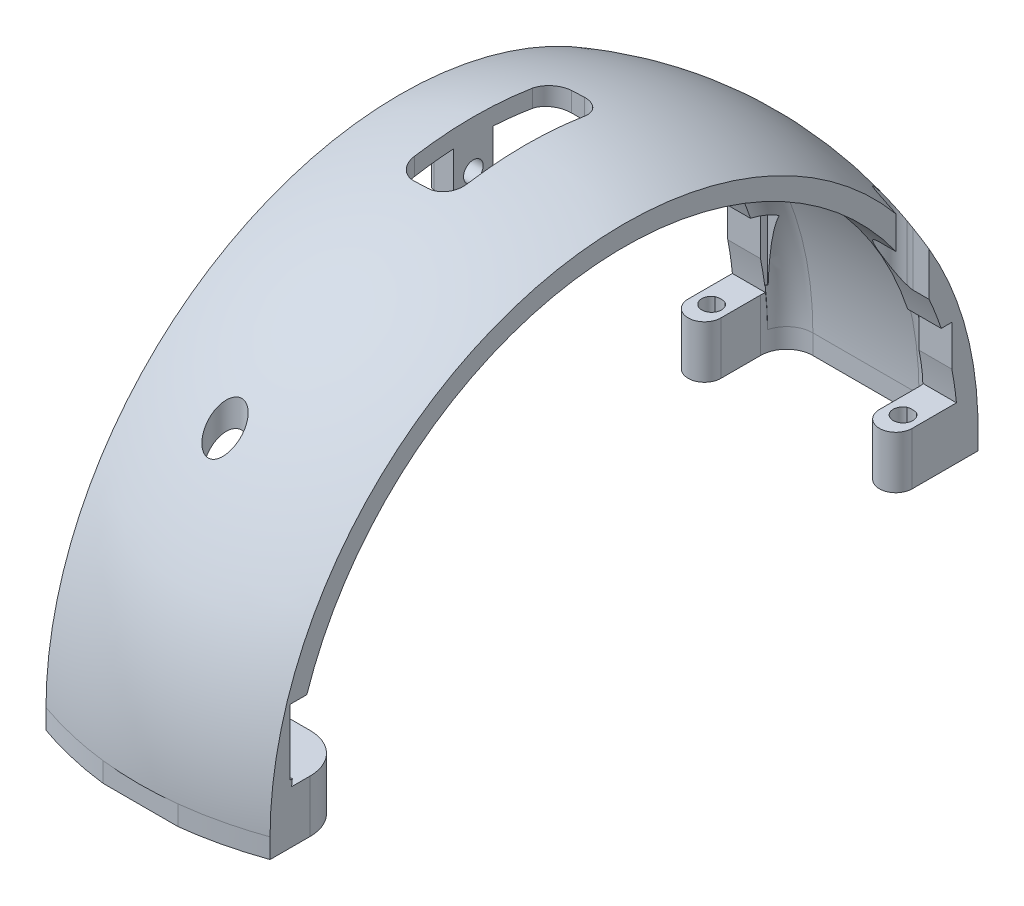
SolidWorks part; units mm, degrees
ref_plane "Front Plane" through (0, 0, 0) normal (0, 0, 1) x (1, 0, 0)
ref_plane "Top Plane" through (0, 0, 0) normal (0, 1, 0) x (1, 0, 0)
ref_plane "Right Plane" through (0, 0, 0) normal (1, 0, 0) x (0, 0, -1)
sketch "Sketch1" plane through (0, 0, 0) normal (0, 1, 0) x (1, 0, 0)
  line L0 (0, 55) -> (0, -55) construction
  line L1 (-55, 0) -> (55, 0)
  line L2 (-55, 20.7263) -> (-55, -21.0382) construction
  line L3 (-6.2, 54.0459) -> (10.01, 54.0459)
  line L4 (-15.2, 44) -> (-10.2, 44)
  line L5 (-15.2, 44) -> (-15.2, 54.0459)
  line L7 (-10.2, 44) -> (-10.2, 50.0459)
  line L12 (1.905, 54.0459) -> (1.905, 57.0459) construction
  line L13 (19.01, 44) -> (14.01, 44)
  line L14 (19.01, 44) -> (19.01, 54.0459)
  line L16 (14.01, 44) -> (14.01, 50.0459)
  line L17 (-10.2, 50.0459) -> (-15.2, 50.0459)
  line L22 (2.5, -41.91) -> (-2.5, -41.91)
  line L23 (2.5, -41.91) -> (2.5, -56.71)
  line L24 (2.5, -56.71) -> (-2.5, -56.71)
  line L25 (-2.5, -41.91) -> (-2.5, -56.71)
  line L26 (14.01, 50.0459) -> (19.01, 50.0459)
  line L27 (-2.5, -48.71) -> (2.5, -48.71)
  line L28 (-2.5, -15.41) -> (2.5, -15.41) construction
  line L29 (-2.5, -52.2226) -> (2.5, -52.2226)
  line L30 (16.51, 41.5) -> (19.01, 41.5)
  line L31 (16.51, 41.5) -> (16.51, 44)
  line L32 (16.51, 44) -> (19.01, 44)
  line L33 (19.01, 41.5) -> (19.01, 44)
  line L34 (-12.7, 41.5) -> (-15.2, 41.5)
  line L35 (-12.7, 41.5) -> (-12.7, 44)
  line L36 (-12.7, 44) -> (-15.2, 44)
  line L37 (-15.2, 41.5) -> (-15.2, 44)
  line L51 (-5, 0) -> (0, 0)
  line L54 (0, -4) -> (0, 4)
  line L55 (-16, 0) -> (-21, 0)
  line L73 (7, -3) -> (4, -3)
  line L74 (-1, 12) -> (1, 12)
  line L75 (-4, 9) -> (-4, -9)
  line L76 (-1, -12) -> (1, -12)
  line L77 (4, 9) -> (4, -9)
  line L78 (-4, 12) -> (4, -12) construction
  line L79 (-4, -12) -> (4, 12) construction
  line L80 (-7, 3) -> (-4, 3)
  line L81 (-8, 2) -> (-8, -2)
  line L82 (-7, -3) -> (-4, -3)
  line L83 (-4, 3) -> (-4, -3)
  line L84 (-8, 3) -> (-4, -3) construction
  line L85 (-8, -3) -> (-4, 3) construction
  line L86 (4, 3) -> (4, -3)
  line L87 (7, 3) -> (4, 3)
  line L88 (8, 2) -> (8, -2)
  line L90 (-35, 51) -> (35, 51)
  line L91 (-35, 51) -> (-35, -51)
  line L92 (-35, -51) -> (35, -51)
  line L93 (35, 51) -> (35, -51)
  line L94 (-35, 51) -> (35, -51) construction
  line L95 (-35, -51) -> (35, 51) construction
  circle A0 centre (0, 0) radius 55 construction
  circle A1 centre (0, -41.91) radius 1.5 construction
  circle A2 centre (16.5327, 45.0784) radius 1.5 construction
  arc A3 (1, -12) -> (4, -9) centre (1, -9) ccw
  circle A4 centre (0, -41.91) radius 1.5
  circle A8 centre (-12.7, 44) radius 2.5
  circle A9 centre (16.51, 44) radius 2.5
  circle A10 centre (0, -41.91) radius 2.5
  arc A11 (14.01, 50.0459) -> (10.01, 54.0459) centre (10.01, 50.0459) ccw
  arc A12 (-6.2, 54.0459) -> (-10.2, 50.0459) centre (-6.2, 50.0459) ccw
  circle A13 centre (0, 0) radius 50 construction
  circle A14 centre (-12.7049, 45.0912) radius 1.5 construction
  circle A15 centre (16.5327, 45.0784) radius 1.5
  circle A16 centre (-12.7049, 45.0912) radius 1.5
  arc A17 (-4, -9) -> (-1, -12) centre (-1, -9) ccw
  arc A18 (1, 12) -> (4, 9) centre (1, 9) cw
  arc A19 (-4, 9) -> (-1, 12) centre (-1, 9) cw
  arc A20 (8, -2) -> (7, -3) centre (7, -2) cw
  arc A21 (8, 2) -> (7, 3) centre (7, 2) ccw
  arc A22 (-8, -2) -> (-7, -3) centre (-7, -2) ccw
  arc A23 (-8, 2) -> (-7, 3) centre (-7, 2) cw
  spline S0 degree 2 poles (-15.2, 54.0459) (1.905, 60.0459) (19.01, 54.0459) knots 0 0 0 1 1 1
  point P59 (-6, 0)
  point P87 (8, -3)
  point P90 (8, 3)
  dimension "D1" = 110
  dimension "D2" = 5
  dimension "D3" = 5
  dimension "D4" = 100
  dimension "D5" = 8
  dimension "D6" = 3
  dimension "D7" = 5
  dimension "D10" = 4
  dimension "D12" = 24
  dimension "D11" = 8
  dimension "D13" = 4
  dimension "D16" = 3
  dimension "D17" = 1
  dimension "D8" = 5
  dimension "D9" = 14.8
  dimension "D14" = 6
  dimension "D15" = 4
  dimension "D18" = 102
  dimension "D19" = 70
extrude "Boss-Extrude1" add sketch "Sketch1" along normal blind 2 contours A16 A8 L7 L17 L5 | S0 L5 L17 A12 L3 A11 L26 L14 | A16 L35 A8 L4 | A16 L4 A8 L35 | A16 A8 L4 | A16 L4 A8 | A8 A16 | A15 A9 L14 L26 L16 | A15 L13 A9 L31 | A15 L31 A9 L13 | A15 L13 A9 | A15 A9 L13 | A9 A15 | A12 L90 L5 L17 | A11 L26 L14 L90 region at (-12.6808, 0, -50.5248) region at (1.905, 0, -54.3281) region at (-12.6999, 0, -47.9735) region at (-14.5064, 0, -44.8299) region at (-13.8029, 0, -42.8825) region at (16.4908, 0, -50.5248) region at (-11.5974, 0, -42.8833) region at (-12.7113, 0, -46.5121) region at (-10.9002, 0, -44.8348) region at (16.5098, 0, -47.9721) region at (14.7243, 0, -44.8518) region at (15.4064, 0, -42.8824) region at (17.6152, 0, -42.8786) region at (18.3266, 0, -44.8292) region at (16.5628, 0, -46.5096)
revolve "Revolve6" add sketch "Sketch1<7>" angle 180 about L1 region at (1.905, 0, -54.3281)
sketch "Sketch1<7>" plane through (0, 0, 0) normal (0, 1, 0) x (1, 0, 0) same geometry as "Sketch1"
extrude "Cut-Extrude1" cut sketch "Sketch1<9>" along normal blind 50 from surface contours A16 L35 A8 L4 | A16 L4 A8 L35 | A16 A8 L4 | A16 L4 A8 | L4 A16 A8 L36 | L36 A16 L35 | L35 A16 L4 | A8 A16 | A9 A15 | L32 A15 A9 L13 | A15 A9 L13 | A15 L13 A9 | A15 L31 A9 L13 | A15 L13 A9 L31 | L13 A15 L31 | L31 A15 L32 | L22 A10 A4 | L22 A4 | L22 A4 | L22 A10 A4 | A9 L30 L33 | A8 L37 L34 region at (-14.5064, 0, -44.8299) region at (-14.6416, 0, -42.0584) region at (-13.8029, 0, -42.8825) region at (0, 0, 39.4659) region at (-2, 0, 41.9659) region at (-12.7048, 0, -45.1835) region at (-13.0962, 0, -43.8342) region at (-11.5974, 0, -42.8833) region at (-12.7113, 0, -46.5121) region at (-10.9002, 0, -44.8348) region at (0, 0, 41.2734) region at (0, 0, 42.5466) region at (-12.3081, 0, -43.8347) region at (14.7243, 0, -44.8518) region at (15.4064, 0, -42.8824) region at (17.6152, 0, -42.8786) region at (18.4516, 0, -42.0584) region at (18.3266, 0, -44.8292) region at (16.5323, 0, -45.1793) region at (16.1205, 0, -43.8304) region at (16.5628, 0, -46.5096) region at (16.9196, 0, -43.8279) starting at face at (-12.7047, 2, -45.0456)
sketch "Sketch1<9>" plane through (0, 0, 0) normal (0, 1, 0) x (1, 0, 0) same geometry as "Sketch1"
extrude "Boss-Extrude2" add sketch "Sketch1<11>" along normal blind 2 and the other way blind 3 separate body contours A10 L25 L27 L23 | L22 A10 A4 | L22 A10 A4 | L25 L29 L23 L27 | L25 L92 L23 L27 | L29 L25 L24 L23 region at (0, 0, 51.6113) region at (0, 0, 49.855) region at (0, 0, 46.2596) region at (0, 0, 54.4663) region at (0, 0, 39.4659) region at (-2, 0, 41.9659)
sketch "Sketch1<11>" plane through (0, 0, 0) normal (0, 1, 0) x (1, 0, 0) same geometry as "Sketch1"
extrude "Boss-Extrude3" add sketch "Sketch1<12>" against normal blind 3 contours A10 L25 L27 L23 | L22 A10 A4 | L22 A10 A4 | S0 L5 L17 A12 L3 A11 L26 L14 | A16 A8 L7 L17 L5 | A15 A9 L14 L26 L16 | A15 L31 A9 L13 | A15 L13 A9 L31 | A16 L35 A8 L4 | A16 L4 A8 L35 | A15 L13 A9 | A15 A9 L13 | A16 L4 A8 | A16 A8 L4 | A9 A15 | A11 L26 L14 L90 | A12 L90 L5 L17 | L92 L25 L29 L23 | L25 L92 L23 L27 region at (-12.6808, 0, -50.5248) region at (1.905, 0, -54.3281) region at (0, 0, 51.6113) region at (0, 0, 49.855) region at (-12.6999, 0, -47.9735) region at (0, 0, 46.2596) region at (-14.5064, 0, -44.8299) region at (-13.8029, 0, -42.8825) region at (16.4908, 0, -50.5248) region at (0, 0, 39.4659) region at (-2, 0, 41.9659) region at (-11.5974, 0, -42.8833) region at (-10.9002, 0, -44.8348) region at (16.5098, 0, -47.9721) region at (14.7243, 0, -44.8518) region at (15.4064, 0, -42.8824) region at (17.6152, 0, -42.8786) region at (18.3266, 0, -44.8292) region at (16.5628, 0, -46.5096)
sketch "Sketch1<12>" plane through (0, 0, 0) normal (0, 1, 0) x (1, 0, 0) same geometry as "Sketch1"
extrude "Cut-Extrude2" cut sketch "Sketch1<13>" along normal blind 70 contours L77 L74 L75 L51 L1 | L77 L1 L51 L75 L76 region at (0, 0, -5.7765) region at (0, 0, 5.7765)
sketch "Sketch1<13>" plane through (0, 0, 0) normal (0, 1, 0) x (1, 0, 0) same geometry as "Sketch1"
extrude "Boss-Extrude5" add sketch "Sketch1<15>" against normal blind 8 from offset 55 contours L88 L1 L77 L73 | L88 L87 L77 L1 | L80 L81 L1 L75 | L81 L82 L75 L1 region at (-5.9676, 0, -1.4768) region at (-5.9676, 0, 1.4768) region at (5.9676, 0, -1.4768) region at (5.9676, 0, 1.4768)
sketch "Sketch1<15>" plane through (0, 0, 0) normal (0, 1, 0) x (1, 0, 0) same geometry as "Sketch1"
sketch "Sketch4" plane through (8, 0, 0) normal (1, 0, 0) x (0, 0, -1)
  line L1 (1.3783, 47) -> (2.8542, 49.4437)
  line L2 (2.8542, 49.4437) -> (1.4759, 51.9437)
  line L3 (2, 47) -> (2, 54.0089)
  line L4 (-2, 54.0089) -> (-2, 47)
  line L5 (-2, 47) -> (2, 47)
  line L6 (2, 47) -> (2, 54.0089)
  line L7 (-2, 54.0089) -> (-2, 47)
  line L8 (-2, 47) -> (2, 47)
  line L9 (1.4759, 51.9437) -> (-1.3783, 52)
  line L10 (-1.3783, 52) -> (-2.8542, 49.5563)
  line L11 (-2.8542, 49.5563) -> (-1.4759, 47.0563)
  line L12 (-1.4759, 47.0563) -> (1.3783, 47)
  circle A0 centre (0, 49.5) radius 1.5
  circle A3 centre (0, 49.5) radius 2.4723 construction
  arc A4 (2, 54.0089) -> (-2, 54.0089) centre (0, 0) ccw
  arc A5 (2, 54.0089) -> (-2, 54.0089) centre (0, 0) ccw
  line M5 (2, 47) -> (2, 54.0089)
  dimension "D2" = 2
  dimension "D4" = 3
  dimension "D3" = 2.5
  dimension "D1" = 0
extrude "Cut-Extrude3" cut sketch "Sketch4" against normal blind 16 contours A0 region at (8, 49.5, 0)
extrude "Cut-Extrude4" cut sketch "Sketch4<3>" against normal blind 3 from surface contours L11 L12 L1 L2 L9 L10 L7 A0 M5 | L10 L11 L7 | L1 L2 M5 | A0 region at (8, 47.0922, 0.0475) region at (8, 49.4887, -2.2847) region at (8, 49.5113, 2.2847) region at (8, 49.5, 0) starting at face at (-8, 49.5, -1.5)
sketch "Sketch4<3>" plane through (8, 0, 0) normal (1, 0, 0) x (0, 0, -1) same geometry as "Sketch4"
extrude "Cut-Extrude5" cut sketch "Sketch1<16>" along normal blind 10 from offset 6 contours L81 A23 L80 L75 A19 L74 A18 L77 L87 A21 L88 L1 L93 L90 L14 L33 L30 A9 L16 A11 A12 L7 A8 L34 L37 L5 L91 | A15 A9 L14 L26 L16 | A16 A8 L7 L17 L5 | A22 L81 L1 L91 L92 L25 A10 L23 L93 L88 A20 L73 L77 A3 L76 A17 L75 L82 | A10 L25 L27 L23 | L25 L92 L23 L27 region at (0, 0, 25.8767) region at (-0.0524, 0, -25.6353) region at (0, 0, 49.855) region at (-12.6999, 0, -47.9735) region at (0, 0, 46.2596) region at (16.5098, 0, -47.9721)
sketch "Sketch1<16>" plane through (0, 0, 0) normal (0, 1, 0) x (1, 0, 0) same geometry as "Sketch1"
extrude "Boss-Extrude6" add sketch "Sketch1<17>" along normal blind 3 from surface contours A16 L4 A8 L35 | A16 L35 A8 L4 | A16 L4 A8 | A16 A8 L4 | A16 A8 L7 L17 L5 | A8 A16 | A15 L31 A9 L13 | A15 L13 A9 L31 | A15 A9 L13 | A15 L13 A9 | A9 A15 | A15 A9 L14 L26 L16 | A10 L25 L27 L23 | L22 A10 A4 | L22 A10 A4 region at (-12.6999, 0, -47.9735) region at (0, 0, 46.2596) region at (-14.5064, 0, -44.8299) region at (-13.8029, 0, -42.8825) region at (0, 0, 39.4659) region at (-2, 0, 41.9659) region at (-11.5974, 0, -42.8833) region at (-12.7113, 0, -46.5121) region at (-10.9002, 0, -44.8348) region at (16.5098, 0, -47.9721) region at (14.7243, 0, -44.8518) region at (15.4064, 0, -42.8824) region at (17.6152, 0, -42.8786) region at (18.3266, 0, -44.8292) region at (16.5628, 0, -46.5096) starting at face at (-12.7047, 2, -45.0456)
sketch "Sketch1<17>" plane through (0, 0, 0) normal (0, 1, 0) x (1, 0, 0) same geometry as "Sketch1"
sketch "Sketch5" plane through (-2.5, 0, 0) normal (-1, 0, 0) x (0, 0, 1)
  line L7 (41.91, -3) -> (56.71, -3)
  line L8 (56.71, -3) -> (56.71, 0)
  line L9 (56.71, 0) -> (54.0459, 0)
  line L10 (54.0089, 2) -> (48.71, 2)
  line L12 (56.71, 0) -> (54.0459, 0)
  line L13 (41.91, 5) -> (41.91, -3)
  line L14 (41.91, -3) -> (56.71, -3)
  line L15 (56.71, -3) -> (56.71, 0)
  line L17 (54.0089, 2) -> (48.71, 2)
  line L20 (41.91, 5) -> (41.91, -3)
  line L22 (48.71, 2) -> (48.71, 5)
  line L24 (48.71, 2) -> (48.71, 5)
  line L25 (48.71, 5) -> (41.91, 5)
  line L26 (48.71, 5) -> (41.91, 5)
  arc A1 (54.0459, 0) -> (54.0089, 2) centre (0, 0) ccw
  arc A4 (54.0459, 0) -> (54.0089, 2) centre (0, 0) ccw
  dimension "D1" = 0
extrude "Boss-Extrude7" add sketch "Sketch5" along normal up to surface (12.7 mm away) up to face at (-15.2, 21.1717, 29.9416)
sketch "Sketch6" plane through (2.5, 0, 0) normal (1, 0, 0) x (0, 0, -1)
  line L7 (-56.71, 0) -> (-56.71, -3)
  line L8 (-56.71, -3) -> (-41.91, -3)
  line L9 (-41.91, -3) -> (-41.91, 5)
  line L10 (-41.91, 5) -> (-48.71, 5)
  line L12 (-48.71, 2) -> (-54.0089, 2)
  line L13 (-41.91, 5) -> (-48.71, 5)
  line L14 (-56.71, 0) -> (-56.71, -3)
  line L15 (-56.71, -3) -> (-41.91, -3)
  line L16 (-41.91, -3) -> (-41.91, 5)
  line L19 (-48.71, 2) -> (-54.0089, 2)
  line L22 (-48.71, 5) -> (-48.71, 2)
  line L24 (-48.71, 5) -> (-48.71, 2)
  line L25 (-54.0459, 0) -> (-56.71, 0)
  line L26 (-54.0459, 0) -> (-56.71, 0)
  arc A1 (-54.0089, 2) -> (-54.0459, 0) centre (0, 0) ccw
  arc A4 (-54.0089, 2) -> (-54.0459, 0) centre (0, 0) ccw
  dimension "D1" = 0
extrude "Boss-Extrude8" add sketch "Sketch6" along normal up to surface (16.51 mm away) up to face at (19.01, 21.1717, 29.9416)
sketch "Sketch7" plane through (0, 2, 0) normal (0, 1, 0) x (1, 0, 0)
  line L3 (19.01, -48.71) -> (-15.2, -48.71)
  line L9 (19.01, -48.71) -> (-15.2, -48.71)
  line L11 (-15.2, -48.71) -> (-15.2, -50.9608)
  line L27 (-15.2, -48.71) -> (-15.2, -50.9608)
  line L28 (-15.2, -50.9608) -> (-10.0845, -50.9608)
  line L29 (-15.2, -50.9608) -> (-10.0845, -50.9608)
  line L30 (-6.2, -54.0089) -> (10.01, -54.0089)
  line L31 (-6.2, -54.0089) -> (10.01, -54.0089)
  line L32 (13.8945, -50.9608) -> (19.01, -50.9608)
  line L33 (13.8945, -50.9608) -> (19.01, -50.9608)
  line L34 (19.01, -50.9608) -> (19.01, -48.71)
  line L35 (19.01, -50.9608) -> (19.01, -48.71)
  spline S2 degree 3 poles (1159.9598, -2811.8848) (55.8288, 25.4078) (-15.9781, -37.4417) (-9.7845, -51.7964) (-9.6805, -51.9911) (-9.4407, -52.3629) (-9.3033, -52.5413) (-9.0043, -52.869) (-8.8426, -53.0191) (-8.4946, -53.2922) (-8.3066, -53.416) (-7.9168, -53.6283) (-7.7149, -53.7173) (-7.297, -53.8618) (-7.0789, -53.9174) (66.8434, -66.2917) (258.5063, 2011.647) (47.595, -3044.1421) knots -8.565706 -8.565706 -8.565706 -8.565706 0.125 0.125 0.25 0.25 0.375 0.375 0.5 0.5 0.625 0.625 0.75 0.75 0.875 0.875 42.952845 42.952845 42.952845 42.952845 only from (-10.0845, -50.9608) to (-6.2, -54.0089)
  spline S3 degree 3 poles (-10.0845, -50.9608) (-10.0318, -51.1757) (-9.9601, -51.3893) (-9.7845, -51.7964) (-9.6805, -51.9911) (-9.4407, -52.3629) (-9.3033, -52.5413) (-9.0043, -52.869) (-8.8426, -53.0191) (-8.4946, -53.2922) (-8.3066, -53.416) (-7.9168, -53.6283) (-7.7149, -53.7173) (-7.297, -53.8618) (-7.0789, -53.9174) (-6.641, -53.9907) (-6.421, -54.0089) (-6.2, -54.0089) knots 0 0 0 0 0.125 0.125 0.25 0.25 0.375 0.375 0.5 0.5 0.625 0.625 0.75 0.75 0.875 0.875 1 1 1 1
  spline S4 degree 3 poles (2971.3147, 418.2625) (-48.2497, 28.9412) (-4.5709, -56.523) (10.8931, -53.9164) (11.1069, -53.8618) (11.525, -53.7173) (11.731, -53.6263) (12.1204, -53.4137) (12.3047, -53.2922) (12.6525, -53.0192) (12.8174, -52.866) (13.1163, -52.5377) (13.2508, -52.3627) (13.4904, -51.9912) (13.5963, -51.7928) (40.3119, 10.3145) (-1561.2349, 562.2577) (2931.0569, -719.8922) knots -8.590086 -8.590086 -8.590086 -8.590086 0.125 0.125 0.25 0.25 0.375 0.375 0.5 0.5 0.625 0.625 0.75 0.75 0.875 0.875 38.800711 38.800711 38.800711 38.800711 only from (10.01, -54.0089) to (13.8945, -50.9608)
  spline S5 degree 3 poles (10.01, -54.0089) (10.2312, -54.0089) (10.4558, -53.9901) (10.8931, -53.9164) (11.1069, -53.8618) (11.525, -53.7173) (11.731, -53.6263) (12.1204, -53.4137) (12.3047, -53.2922) (12.6525, -53.0192) (12.8174, -52.866) (13.1163, -52.5377) (13.2508, -52.3627) (13.4904, -51.9912) (13.5963, -51.7928) (13.7718, -51.3847) (13.8419, -51.1754) (13.8945, -50.9608) knots 0 0 0 0 0.125 0.125 0.25 0.25 0.375 0.375 0.5 0.5 0.625 0.625 0.75 0.75 0.875 0.875 1 1 1 1
  dimension "D1" = 0
extrude "Boss-Extrude9" add sketch "Sketch7" along normal up to surface (3 mm away) up to face at (1.27, 5, 43.76)
sketch "Sketch9" plane through (0, 0, 0) normal (0, 1, 0) x (1, 0, 0)
  line L2 (7.6286, -56.71) -> (19.01, -56.71)
  line L3 (19.01, -56.71) -> (19.01, -54.0459)
  line L4 (7.6286, -56.71) -> (19.01, -56.71)
  line L5 (19.01, -56.71) -> (19.01, -54.0459)
  line L6 (-15.2, -54.0459) -> (-15.2, -56.71)
  line L7 (-15.2, -56.71) -> (-3.8186, -56.71)
  line L8 (-15.2, -54.0459) -> (-15.2, -56.71)
  line L9 (-15.2, -56.71) -> (-3.8186, -56.71)
  parabola Q1 (19.01, -54.0459) -> (7.6286, -56.71) focus (1.905, -32.6642) apex (1.905, -57.0459)
  parabola Q2 (19.01, -54.0459) -> (7.6286, -56.71) focus (1.905, -32.6642) apex (1.905, -57.0459)
  parabola Q3 (-3.8186, -56.71) -> (-15.2, -54.0459) focus (1.905, -32.6642) apex (1.905, -57.0459)
  parabola Q4 (-3.8186, -56.71) -> (-15.2, -54.0459) focus (1.905, -32.6642) apex (1.905, -57.0459)
  dimension "D1" = 0
  dimension "D2" = 0
extrude "Cut-Extrude6" cut sketch "Sketch9" against normal blind 4
sketch "Sketch10" plane through (0, 2, 0) normal (0, 1, 0) x (1, 0, 0)
  line L2 (14.01, 50.0459) -> (19.01, 50.0459)
  line L4 (14.01, 50.0459) -> (19.01, 50.0459)
  line L9 (-15.2, 50.0459) -> (-10.2, 50.0459)
  line L10 (-15.2, 50.0459) -> (-10.2, 50.0459)
  line L11 (-10.094, 50.9608) -> (-15.2, 50.9608)
  line L15 (-10.094, 50.9608) -> (-15.2, 50.9608)
  line L17 (19.01, 50.0459) -> (19.01, 50.9608)
  line L18 (19.01, 50.0459) -> (19.01, 50.9608)
  line L19 (19.01, 50.9608) -> (13.904, 50.9608)
  line L20 (19.01, 50.9608) -> (13.904, 50.9608)
  line L21 (-15.2, 50.9608) -> (-15.2, 50.0459)
  line L22 (-15.2, 50.9608) -> (-15.2, 50.0459)
  arc A1 (14.01, 50.0459) -> (13.904, 50.9608) centre (10.01, 50.0459) ccw
  arc A3 (14.01, 50.0459) -> (13.904, 50.9608) centre (10.01, 50.0459) ccw
  arc A5 (-10.094, 50.9608) -> (-10.2, 50.0459) centre (-6.2, 50.0459) ccw
  arc A6 (-10.094, 50.9608) -> (-10.2, 50.0459) centre (-6.2, 50.0459) ccw
  dimension "D1" = 0
  dimension "D2" = 0
extrude "Boss-Extrude10" add sketch "Sketch10" along normal up to surface (3 mm away) up to face at (-12.7, 5, -46.398)
sketch "Sketch12" plane through (0, 5, 0) normal (0, 1, 0) x (1, 0, 0)
  line L0 (16.5642, 46.578) -> (19.01, 46.578)
  line L1 (16.5642, 46.578) -> (14.01, 46.578)
  line L3 (19.01, 44) -> (19.01, 50.7543)
  line L4 (19.01, 50.7543) -> (13.9468, 50.7543)
  line L5 (14.01, 50.0459) -> (14.01, 44)
  line L6 (19.01, 44) -> (19.01, 50.7543)
  line L7 (19.01, 50.7543) -> (13.9468, 50.7543)
  line L8 (14.01, 50.0459) -> (14.01, 44)
  arc A0 (17.282, 46.3778) -> (15.8387, 46.4082) centre (16.5327, 45.0784) ccw construction
  arc A1 (15.8387, 46.4082) -> (16.51, 41.5) centre (16.51, 44) ccw construction
  arc A2 (14.01, 50.0459) -> (13.9468, 50.7543) centre (10.01, 50.0459) ccw
  arc A3 (14.01, 44) -> (19.01, 44) centre (16.51, 44) ccw
  arc A4 (14.01, 50.0459) -> (13.9468, 50.7543) centre (10.01, 50.0459) ccw
  arc A5 (14.01, 44) -> (19.01, 44) centre (16.51, 44) ccw
  arc A6 (19.01, 44) -> (17.282, 46.3778) centre (16.51, 44) ccw construction
  arc A7 (15.8387, 46.4082) -> (16.51, 41.5) centre (16.51, 44) ccw
  arc A8 (19.01, 44) -> (17.282, 46.3778) centre (16.51, 44) ccw
  arc A9 (17.282, 46.3778) -> (15.8387, 46.4082) centre (16.5327, 45.0784) ccw
  line M6 (19.01, 44) -> (19.01, 50.7543)
  dimension "D1" = 0
extrude "Cut-Extrude8" cut sketch "Sketch12" along normal up to surface (23.9514 mm away) contours A9 A8 L0 M6 region at (18.4085, 5, -46.0034) up to face at (0.3682, 56.0618, 0)
sketch "Sketch13" plane through (0, 5, 0) normal (0, 1, 0) x (1, 0, 0)
  line L0 (-12.7117, 46.5912) -> (-10.2, 46.5912)
  line L1 (-12.7117, 46.5912) -> (-15.2, 46.5912)
  line L3 (-10.2, 44) -> (-10.2, 50.0459)
  line L4 (-10.1368, 50.7543) -> (-15.2, 50.7543)
  line L5 (-15.2, 50.7543) -> (-15.2, 44)
  line L6 (-10.2, 44) -> (-10.2, 50.0459)
  line L7 (-10.1368, 50.7543) -> (-15.2, 50.7543)
  line L8 (-15.2, 50.7543) -> (-15.2, 44)
  arc A0 (-11.9405, 46.3818) -> (-13.4809, 46.3749) centre (-12.7049, 45.0912) ccw construction
  arc A1 (-13.4809, 46.3749) -> (-15.2, 44) centre (-12.7, 44) ccw construction
  arc A2 (-10.1368, 50.7543) -> (-10.2, 50.0459) centre (-6.2, 50.0459) ccw
  arc A3 (-15.2, 44) -> (-10.2, 44) centre (-12.7, 44) ccw
  arc A4 (-10.1368, 50.7543) -> (-10.2, 50.0459) centre (-6.2, 50.0459) ccw
  arc A5 (-15.2, 44) -> (-10.2, 44) centre (-12.7, 44) ccw
  arc A6 (-12.7, 41.5) -> (-11.9405, 46.3818) centre (-12.7, 44) ccw construction
  arc A7 (-11.9405, 46.3818) -> (-13.4809, 46.3749) centre (-12.7049, 45.0912) ccw
  arc A8 (-13.4809, 46.3749) -> (-15.2, 44) centre (-12.7, 44) ccw
  arc A9 (-12.7, 41.5) -> (-11.9405, 46.3818) centre (-12.7, 44) ccw
  line M9 (-15.2, 50.7543) -> (-15.2, 44)
  dimension "D1" = 0
extrude "Cut-Extrude9" cut sketch "Sketch13" along normal up to surface (22.3901 mm away) contours A8 A7 L1 M9 region at (-14.591, 5, -46.0137) up to face at (1.2345, 19.1081, -14.5043)
fillet "Fillet8" radius 6 2 edges at (-15.2, 1, 41.91) (19.01, 1, 41.91)
